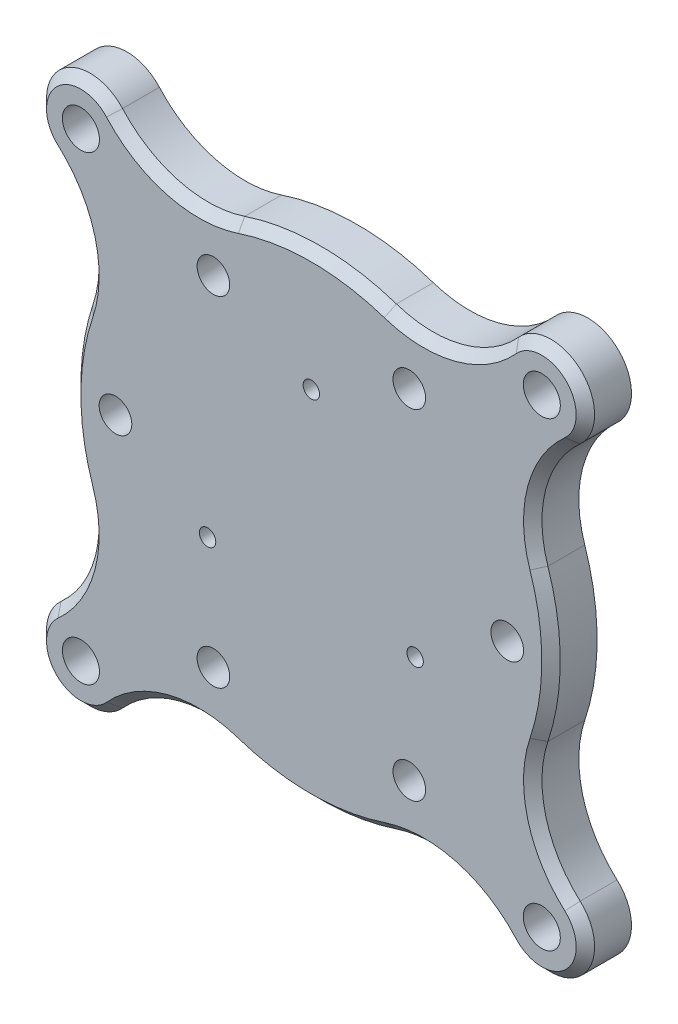
SolidWorks part; units mm, degrees
material "6061-T6 (SS)"
ref_plane "Front Plane" through (0, 0, 0) normal (0, 0, 1) x (1, 0, 0)
ref_plane "Top Plane" through (0, 0, 0) normal (0, 1, 0) x (1, 0, 0)
ref_plane "Right Plane" through (0, 0, 0) normal (1, 0, 0) x (0, 0, -1)
sketch "Sketch1" plane through (0, 0, 0) normal (0, 0, 1) x (1, 0, 0)
  circle A0 centre (0, 0) radius 53.975
  dimension "D1" = 107.95
extrude "Boss-Extrude1" add sketch "Sketch1" along normal blind 6.35
hole_wizard "CSK for #8 Flat Head Machine Screw1" positions "Sketch2" profile "Sketch3" countersink size "#8" standard "ANSI Inch" end condition through all
sketch "Sketch2" plane through (0, 0, 0) normal (0, 0, -1) x (-1, 0, 0)
  line L0 (-13.4937, 23.3719) -> (0, 0) construction
  line L1 (0, 0) -> (0, 26.9875) construction
  circle A0 centre (0, 0) radius 26.9875
  point P5 (-13.4937, 23.3719)
  dimension "D1" = 53.975
  dimension "D2" = 30
sketch "Sketch3" plane through (13.4937, 23.3719, 0) normal (1, 0, 0) x (0, 1, 0)
  line L0 (0, 0) -> (0, 6.35)
  line L1 (0, 6.35) -> (2.2479, 6.35)
  line L2 (2.2479, 6.35) -> (2.2479, 3.0265)
  line L3 (2.2479, 3.0265) -> (4.8788, 0)
  line L5 (4.8788, 0) -> (0, 0)
  line L6 (-2.2479, 3.0265) -> (-4.8788, 0) construction
  line L11 (0, -6.35) -> (0, 107.95) construction
  dimension "Thru Hole Dia." = 4.4958
  dimension "Thru Hole Depth" = 6.35
  dimension "Near C'Sink Dia." = 9.7576
  dimension "Near C'Sink Angle" = 82
pattern_circular "CirPattern1" count 6 over 360 about axis through (0, 0, 6.35) along (0, 0, -1) of "CSK for #8 Flat Head Machine Screw1"
hole_wizard "#10 Clearance Hole1" positions "Sketch4" profile "Sketch5" hole size "#10" standard "ANSI Inch" end condition through all
sketch "Sketch4" plane through (0, 0, 6.35) normal (0, 0, 1) x (1, 0, 0)
  line L0 (0, 44.9013) -> (0, 0) construction
  line L1 (0, 0) -> (31.75, 31.75) construction
  circle A0 centre (0, 0) radius 44.9013
  point P9 (31.75, 31.75)
  dimension "D1" = 31.75
  dimension "D2" = 45
sketch "Sketch5" plane through (31.75, 31.75, 6.35) normal (1, 0, 0) x (0, -1, 0)
  line L0 (0, 0) -> (0, 6.35)
  line L1 (0, 6.35) -> (2.5527, 6.35)
  line L2 (2.5527, 6.35) -> (2.5527, 0)
  line L5 (2.5527, 0) -> (0, 0)
  line L11 (0, -6.35) -> (0, 107.95) construction
  dimension "Thru Hole Dia." = 5.1054
  dimension "Thru Hole Depth" = 6.35
pattern_circular "CirPattern2" count 4 over 360 about axis through (0, 0, 6.35) along (0, 0, -1) of "#10 Clearance Hole1"
hole_wizard "#4-40 Tapped Hole1" positions "Sketch6" profile "Sketch7" tap size "#4-40" standard "ANSI Inch" end condition through all
sketch "Sketch6" plane through (0, 0, 6.35) normal (0, 0, 1) x (1, 0, 0)
  circle A0 centre (0, 0) radius 16.51
  point P5 (0, 16.51)
  dimension "D1" = 33.02
sketch "Sketch7" plane through (0, 16.51, 6.35) normal (1, 0, 0) x (0, -1, 0)
  line L0 (0, 0) -> (0, 6.35)
  line L1 (0, 6.35) -> (1.1303, 6.35)
  line L2 (1.1303, 6.35) -> (1.1303, 0)
  line L5 (1.1303, 0) -> (0, 0)
  line L11 (0, -6.35) -> (0, 107.95) construction
  dimension "Thru Tap Drill Dia." = 2.2606
  dimension "Thru Tap Drill Depth" = 6.35
cosmetic thread "Hole Thread1" parameters "D2"=2.8448
pattern_circular "CirPattern3" count 3 over 360 about axis through (0, 0, 6.35) along (0, 0, -1) of "#4-40 Tapped Hole1"
sketch "Sketch9" plane through (0, 0, 0) normal (0, 0, -1) x (-1, 0, 0)
  line L0 (-35.9977, 35.9977) -> (-38.1661, 38.1661)
  line L1 (38.1661, 38.1661) -> (35.9977, 35.9977)
  arc A0 (-27.283, 35.7664) -> (-35.9977, 35.9977) centre (-31.75, 31.75) ccw
  arc A1 (10.4527, 31.3219) -> (-10.4527, 31.3219) centre (0, 0) ccw
  arc A2 (35.9977, 35.9977) -> (27.283, 35.7664) centre (31.75, 31.75) ccw
  circle A5 centre (0, 0) radius 53.975 construction
  arc A6 (38.1661, 38.1661) -> (-38.1661, 38.1661) centre (0, 0) ccw
  arc A8 (10.4527, 31.3219) -> (27.283, 35.7664) centre (15.4781, 46.3805) ccw
  arc A9 (-27.283, 35.7664) -> (-10.4527, 31.3219) centre (-15.4781, 46.3805) ccw
  point P1 (29.1654, 35.7199)
  point P4 (-18.2696, 38.1661)
  point P7 (10.4191, 29.9917)
  point P21 (-16.2659, 43.5226)
  dimension "D1" = 12.0142
  dimension "D2" = 33.02
  dimension "D3" = 15.875
extrude "Cut-Extrude2" cut sketch "Sketch9" against normal through all
pattern_circular "CirPattern4" count 4 over 360 about axis through (0, 0, 6.35) along (0, 0, -1) of "Cut-Extrude2"
chamfer "Chamfer1" distance 1.27 angle 45 16 edges at (-33.02, 0, 6.35) (-31.0317, -19.5314, 6.35) (-31.0317, 19.5314, 6.35) (-35.9977, -35.9977, 6.35) (-35.9977, 35.9977, 6.35) (-19.5314, -31.0317, 6.35) (-19.5314, 31.0317, 6.35) (0, -33.02, 6.35) (0, 33.02, 6.35) (19.5314, -31.0317, 6.35) (19.5314, 31.0317, 6.35) (35.9977, -35.9977, 6.35) (35.9977, 35.9977, 6.35) (31.0317, -19.5314, 6.35) (31.0317, 19.5314, 6.35) (33.02, 0, 6.35)
